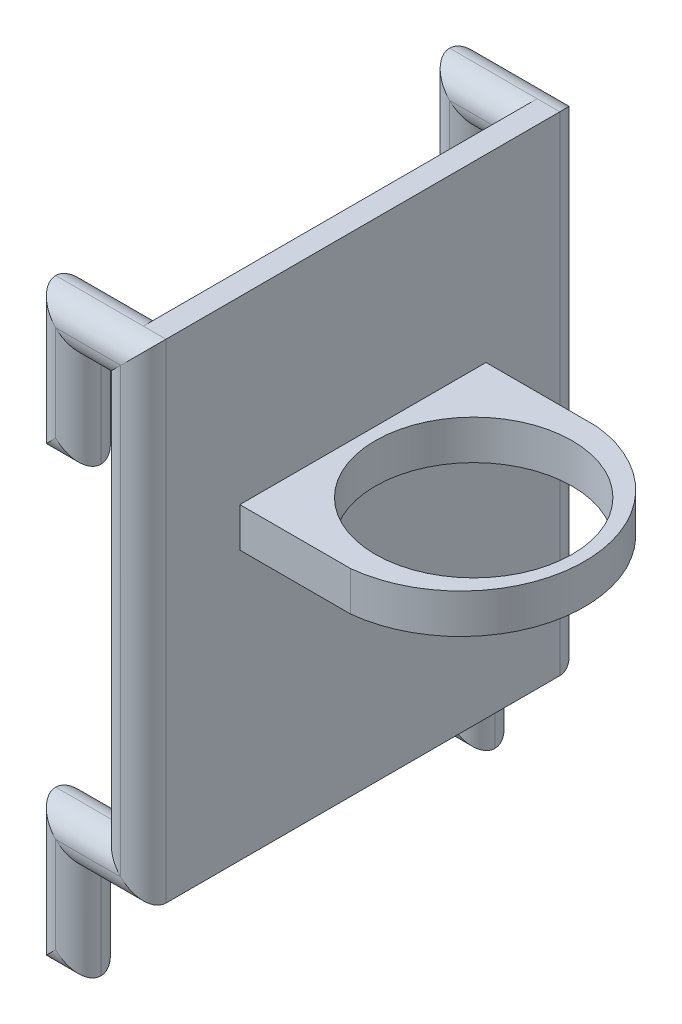
SolidWorks part; units mm, degrees
ref_plane "Plan de face" through (0, 0, 0) normal (0, 0, 1) x (1, 0, 0)
ref_plane "Plan de dessus" through (0, 0, 0) normal (0, 1, 0) x (1, 0, 0)
ref_plane "Plan de droite" through (0, 0, 0) normal (1, 0, 0) x (0, 0, -1)
sketch "Esquisse1" plane through (0, 0, 0) normal (0, 0, 1) x (1, 0, 0)
  line L0 (0, 0) -> (-6.6, 0)
  line L1 (-6.6, 0) -> (-6.6, -12)
  line L2 (0, 0) -> (0, -45)
  line L3 (0, -45) -> (-6.6, -45)
  line L4 (-6.6, -45) -> (-6.6, -57)
  dimension "D1" = 45
  dimension "D2" = 12
  dimension "D3" = 6.6
extrude "Extru.-Mince1" add sketch "Esquisse1" along normal mid plane 4.6 thin
fillet "Congé1" radius 2.3 24 edges at (-6.6, -57, -2.3) (-4.3, -52.15, -2.3) (-1, -47.3, -2.3) (2.3, -22.5, -2.3) (-3.3, 2.3, -2.3) (-8.9, -4.85, -2.3) (-6.6, -12, -2.3) (-4.3, -7.15, -2.3) (-3.3, -2.3, -2.3) (-2.3, -22.5, -2.3) (-5.6, -42.7, -2.3) (-8.9, -49.85, -2.3) (-5.6, -42.7, 2.3) (-2.3, -22.5, 2.3) (-3.3, -2.3, 2.3) (-4.3, -7.15, 2.3) (-6.6, -12, 2.3) (-8.9, -4.85, 2.3) (-3.3, 2.3, 2.3) (2.3, -22.5, 2.3) (-1, -47.3, 2.3) (-4.3, -52.15, 2.3) (-6.6, -57, 2.3) (-8.9, -49.85, 2.3)
sketch "Esquisse2" plane through (0, 0, 0) normal (1, 0, 0) x (0, 0, -1)
  line L1 (0, -47.3) -> (-40, -47.3)
  line L2 (0, -47.3) -> (0, 2.3)
  line L3 (0, 2.3) -> (-40, 2.3)
  line L4 (-40, -47.3) -> (-40, 2.3)
  dimension "D1" = 40
extrude "Boss.-Extru.1" add sketch "Esquisse2" along normal up to vertex (2.3 mm away) up to point (2.3, 2.3, 0)
pattern_linear "Répétition linéaire1" count 2 spacing 40 along (0, 0, 1) of "Extru.-Mince1"
fillet "Congé2" radius 2.3 23 edges at (-5.6, -42.7, 42.3) (-2.3, -22.5, 42.3) (-3.3, -2.3, 42.3) (-4.3, -7.15, 42.3) (-6.6, -12, 42.3) (-8.9, -4.85, 42.3) (-3.3, 2.3, 42.3) (2.3, -22.5, 42.3) (-6.6, -57, 42.3) (-4.3, -52.15, 42.3) (-1, -47.3, 42.3) (-8.9, -49.85, 42.3) (-2.15, -47.3, 37.7) (-4.3, -52.15, 37.7) (-6.6, -57, 37.7) (-8.9, -49.85, 37.7) (-5.6, -42.7, 37.7) (-2.3, -22.5, 37.7) (-3.3, -2.3, 37.7) (-4.3, -7.15, 37.7) (-6.6, -12, 37.7) (-8.9, -4.85, 37.7) (-4.45, 2.3, 37.7)
sketch "Esquisse3" plane through (0, 0, 0) normal (0, 1, 0) x (1, 0, 0)
  line L0 (2.3, 0) -> (2.3, -40) construction
  line L1 (2.3, -7.5) -> (13.55, -7.5)
  line L2 (2.3, -7.5) -> (2.3, -32.5)
  line L3 (2.3, -32.5) -> (13.55, -32.5)
  circle A0 centre (13.55, -20) radius 10
  arc A1 (13.55, -7.5) -> (13.55, -32.5) centre (12.2306, -20) cw
  point P1 (0, 0)
  point P3 (0, 0)
  point P6 (2.3, -20)
  point P9 (13.55, -20)
  point P10 (0, 0)
  point P11 (0, 0)
  point P12 (24.8, -20)
  point P13 (7.925, -7.5)
  dimension "D3" = 20
  dimension "D1" = 25
  dimension "D2" = 11.25
  dimension "D4" = 11.25
extrude "Boss.-Extru.2" add sketch "Esquisse3" along normal blind 4 from offset 20
